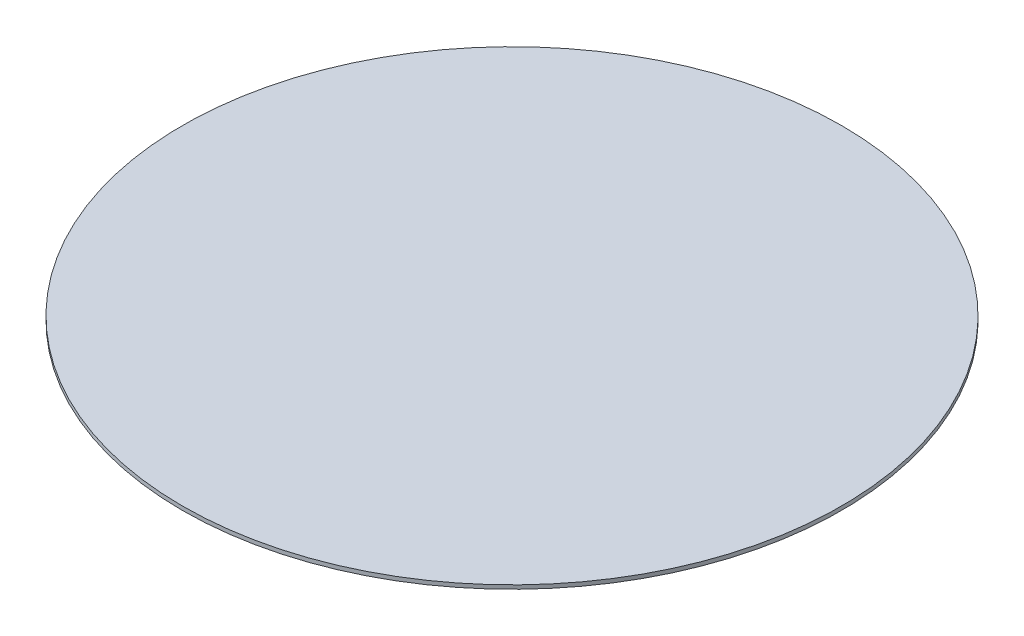
SolidWorks part; units mm, degrees
ref_plane "Front Plane" through (0, 0, 0) normal (0, 0, 1) x (1, 0, 0)
ref_plane "Top Plane" through (0, 0, 0) normal (0, 1, 0) x (1, 0, 0)
ref_plane "Right Plane" through (0, 0, 0) normal (1, 0, 0) x (0, 0, -1)
sketch "Sketch1" plane through (0, 0, 0) normal (0, 1, 0) x (1, 0, 0)
  circle A0 centre (0, 0) radius 10.8437
  dimension "D1" = 21.6875
extrude "Boss-Extrude1" add sketch "Sketch1" along normal blind 0.127
equation "\"magnet_inset\"= 0.0625in"
equation "\"magnet_diameter\" = 0.2in"
equation "\"steel_inset_distance\" = 1in / 32"
equation "\"kapton_thickness\"= 0.005in"
equation "\"pcb_thickness\"= 0.6mm"
equation "\"magnet_thickness\" = 0.03125in"
equation "\"edge_radius\" = 1in / 10"
equation "\"card_width\" = 78mm"
equation "\"card_height\" = 50mm"
equation "\"battery_diameter\" = 20mm"
equation "\"battery_oversize\" = 0.1mm"
equation "\"battery_vertical_inset\" = 1in / 16"
equation "\"battery_horizontal_inset\" = 1in / 4"
equation "\"battery_spacing\" = 1in / 16"
equation "\"battery_thickness\" = 1.6mm"
equation "\"battery_cap_oversize\" = 1in / 16"
equation "\"D1@Sketch1\"=\"battery_diameter\"+\"battery_oversize\"+\"battery_cap_oversize\""
equation "\"battery_cap_thickness\" = 0.005in"
equation "\"D1@Boss-Extrude1\"=\"battery_cap_thickness\""
